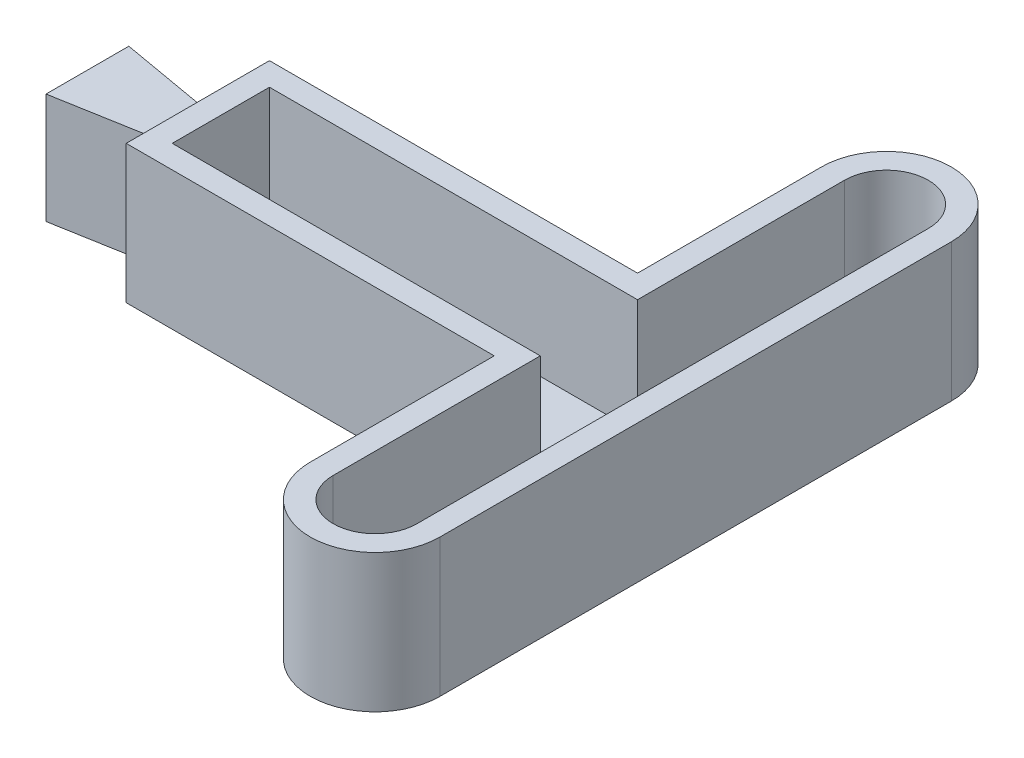
SolidWorks part; units mm, degrees
ref_plane "Front Plane" through (0, 0, 0) normal (0, 0, 1) x (1, 0, 0)
ref_plane "Top Plane" through (0, 0, 0) normal (0, 1, 0) x (1, 0, 0)
ref_plane "Right Plane" through (0, 0, 0) normal (1, 0, 0) x (0, 0, -1)
sketch "Sketch1" plane through (0, 0, 0) normal (0, 1, 0) x (1, 0, 0)
  line L0 (0, 11.43) -> (0, -11.43)
  line L1 (0, 11.43) -> (30.48, 6.0556)
  line L2 (0, -11.43) -> (30.48, -6.0556)
  line L3 (30.48, 6.0556) -> (30.48, 19.7716)
  line L4 (30.48, -6.0556) -> (30.48, -19.7716)
  line L5 (30.48, 6.0556) -> (30.48, -6.0556) construction
  line L6 (0, 0) -> (30.48, 0) construction
  line L7 (30.48, 19.7716) -> (132.08, 19.7716)
  line L8 (30.48, -19.7716) -> (132.08, -19.7716)
  line L9 (132.08, 19.7716) -> (132.08, 70.5716)
  line L10 (132.08, -19.7716) -> (132.08, -70.5716)
  line L12 (167.894, 70.5716) -> (167.894, -70.5716)
  arc A0 (167.894, 70.5716) -> (132.08, 70.5716) centre (149.987, 70.5716) ccw
  arc A1 (167.894, -70.5716) -> (132.08, -70.5716) centre (149.987, -70.5716) cw
  point P3 (0, 0)
  dimension "D1" = 22.86
  dimension "D2" = 30.48
  dimension "D3" = 80
  dimension "D4" = 80
  dimension "D5" = 39.5431
  dimension "D6" = 13.716
  dimension "D7" = 101.6
  dimension "D8" = 101.6
  dimension "D9" = 13.716
  dimension "D10" = 50.8
  dimension "D11" = 35.814
extrude "Boss-Extrude1" add sketch "Sketch1" along normal blind 38.1
sketch "Sketch5" plane through (0, 38.1, 0) normal (0, 1, 0) x (1, 0, 0)
  line L0 (0, -11.43) -> (0, 11.43)
  line L1 (0, -11.43) -> (30.48, -6.0556) construction
  line L2 (0, 11.43) -> (0, -11.43) construction
  line L3 (0, 11.43) -> (0.2056, 11.5763)
  line L4 (30.48, 6.0556) -> (30.48, -6.0556)
  line L5 (30.48, -6.0556) -> (0, -11.43)
  line L6 (0.2056, 11.5763) -> (30.48, 6.0556)
  dimension "D1" = 79.665
extrude "Cut-Extrude10" cut sketch "Sketch5" against normal blind 7.62
shell "Shell2" thickness 6.35 removed face at (115.6335, 38.1, 0)
